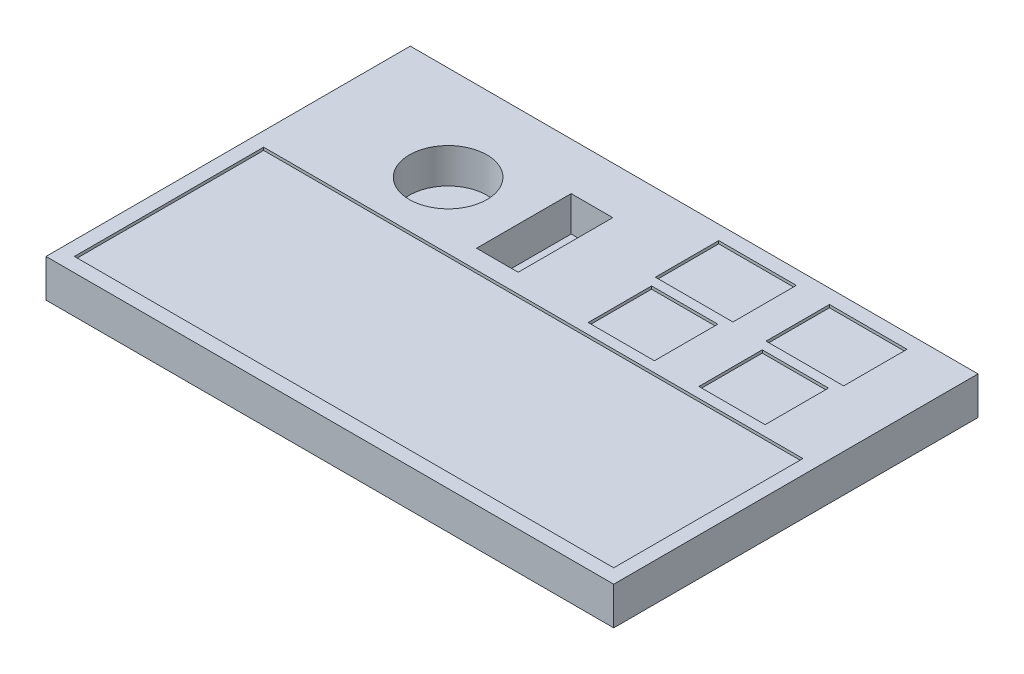
SolidWorks part; units mm, degrees
ref_plane "Front Plane" through (0, 0, 0) normal (0, 0, 1) x (1, 0, 0)
ref_plane "Top Plane" through (0, 0, 0) normal (0, 1, 0) x (1, 0, 0)
ref_plane "Right Plane" through (0, 0, 0) normal (1, 0, 0) x (0, 0, -1)
sketch "Sketch1" plane through (0, 0, 0) normal (0, 1, 0) x (1, 0, 0)
  line L1 (-300, 192.5) -> (300, 192.5)
  line L2 (-300, 192.5) -> (-300, -192.5)
  line L3 (-300, -192.5) -> (300, -192.5)
  line L4 (300, 192.5) -> (300, -192.5)
  line L5 (-300, 192.5) -> (300, -192.5) construction
  line L6 (-300, -192.5) -> (300, 192.5) construction
  point P0 (0, 0)
  dimension "D1" = 600
  dimension "D2" = 385
extrude "Boss-Extrude1" add sketch "Sketch1" against normal blind 40
sketch "Sketch2" plane through (0, 0, 0) normal (0, 1, 0) x (1, 0, 0)
  line L0 (-300, 192.5) -> (-300, -192.5) construction
  line L1 (-80, 142.5) -> (-36, 142.5)
  line L2 (-80, 142.5) -> (-80, 42.5)
  line L3 (-80, 42.5) -> (-36, 42.5)
  line L4 (-36, 142.5) -> (-36, 42.5)
  line L5 (41, 177.5) -> (123, 177.5)
  line L6 (41, 177.5) -> (41, 110.5)
  line L7 (41, 110.5) -> (123, 110.5)
  line L8 (123, 177.5) -> (123, 110.5)
  line L9 (158, 177.5) -> (240, 177.5)
  line L10 (158, 177.5) -> (158, 110.5)
  line L11 (158, 110.5) -> (240, 110.5)
  line L12 (240, 177.5) -> (240, 110.5)
  line L13 (47, 100.5) -> (117, 100.5)
  line L14 (47, 100.5) -> (47, 33.5)
  line L15 (47, 33.5) -> (117, 33.5)
  line L16 (117, 100.5) -> (117, 33.5)
  line L17 (164, 100.5) -> (234, 100.5)
  line L18 (164, 100.5) -> (164, 33.5)
  line L19 (164, 33.5) -> (234, 33.5)
  line L20 (234, 100.5) -> (234, 33.5)
  line L21 (-285, 22.5) -> (285, 22.5)
  line L22 (-285, 22.5) -> (-285, -177.5)
  line L23 (-285, -177.5) -> (285, -177.5)
  line L24 (285, 22.5) -> (285, -177.5)
  line L25 (300, -192.5) -> (300, 192.5) construction
  line L26 (-300, -192.5) -> (300, -192.5) construction
  line L28 (300, 192.5) -> (-300, 192.5) construction
  circle A0 centre (-160, 92.5) radius 41
  point P34 (-80, 92.5)
  point P36 (82, 100.5)
  point P37 (82, 110.5)
  point P38 (164, 67)
  point P39 (117, 67)
  point P40 (199, 110.5)
  point P41 (199, 100.5)
  dimension "D1" = 82
  dimension "D7" = 100
  dimension "D6" = 140
  dimension "D2" = 15
  dimension "D3" = 15
  dimension "D4" = 15
  dimension "D5" = 200
  dimension "D8" = 44
  dimension "D9" = 100
  dimension "D10" = 220
  dimension "D11" = 70
  dimension "D12" = 67
  dimension "D13" = 82
  dimension "D14" = 67
  dimension "D15" = 60
  dimension "D16" = 15
  dimension "D17" = 10
  dimension "D18" = 35
extrude "Cut-Extrude1" cut sketch "Sketch2" against normal blind 3 contours L8 L5 L6 L7 | L12 L9 L10 L11 | L20 L17 L18 L19 | L24 L21 L22 L23 | L21 L24 L23 L22 | L14 L15 L16 L13 region at (82, 0, -144) region at (199, 0, -144) region at (199, 0, -67) region at (0, 0, 77.5)
extrude "Cut-Extrude2" cut sketch "Sketch2<3>" against normal offset from surface (37 mm away) 3 contours A0 | L4 L1 L2 L3 region at (-58, 0, -92.5) region at (-160, 0, -92.5) up to face at (0, -40, 0)
sketch "Sketch2<3>" plane through (0, 0, 0) normal (0, 1, 0) x (1, 0, 0) same geometry as "Sketch2"
